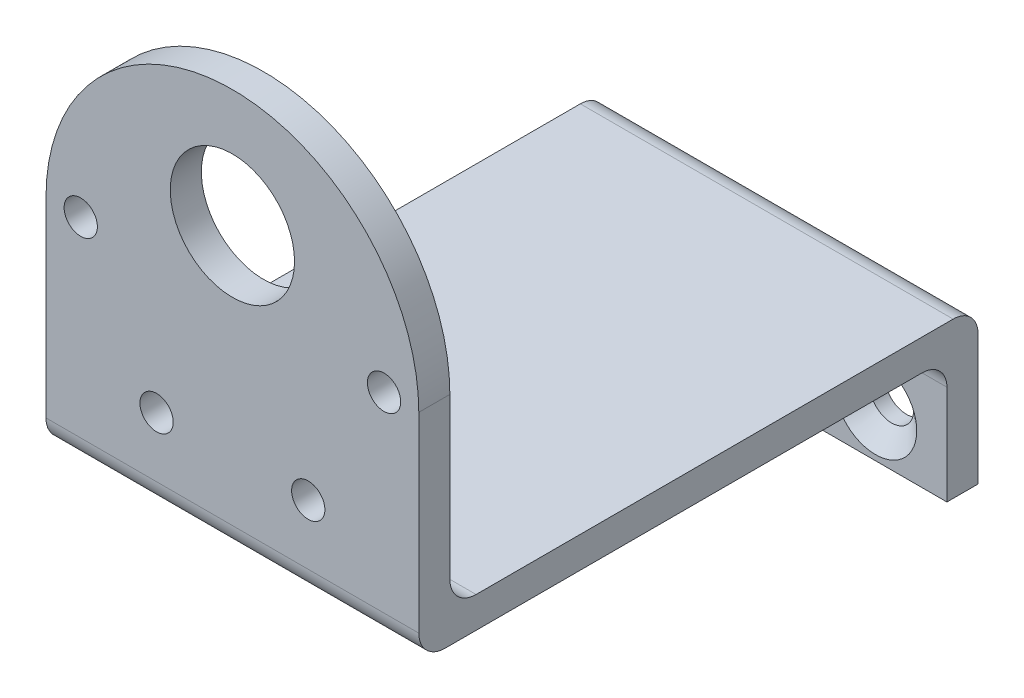
SolidWorks part; units mm, degrees
ref_plane "Front Plane" through (0, 0, 0) normal (0, 0, 1) x (1, 0, 0)
ref_plane "Top Plane" through (0, 0, 0) normal (0, 1, 0) x (1, 0, 0)
ref_plane "Right Plane" through (0, 0, 0) normal (1, 0, 0) x (0, 0, -1)
sketch "Sketch1" plane through (0, 0, 0) normal (1, 0, 0) x (0, 0, -1)
  line L0 (0, 42.0944) -> (0, 6.6753)
  line L1 (2.681, 3.9944) -> (51.435, 3.9944)
  line L3 (0, 42.0944) -> (-3.175, 42.0944)
  line L4 (-3.175, 42.0944) -> (-3.175, 3.5003)
  line L5 (-0.494, 0.8194) -> (48.26, 0.8194)
  line L8 (53.975, 1.4544) -> (53.975, -11.8806)
  line L9 (53.975, -11.8806) -> (50.8, -11.8806)
  line L10 (50.8, -11.8806) -> (50.8, -1.7206)
  arc A2 (-3.175, 3.5003) -> (-0.494, 0.8194) centre (-0.494, 3.5003) ccw
  arc A3 (0, 6.6753) -> (2.681, 3.9944) centre (2.681, 6.6753) ccw
  arc A4 (51.435, 3.9944) -> (53.975, 1.4544) centre (51.435, 1.4544) cw
  arc A5 (48.26, 0.8194) -> (50.8, -1.7206) centre (48.26, -1.7206) cw
  point P14 (52.3875, -11.8806)
  dimension "D2" = 2.54
  dimension "D1" = 3.175
  dimension "D3" = 3.175
  dimension "D4" = 12.7
  dimension "D6" = 57.15
  dimension "D7" = 3.175
  dimension "D5" = 38.1
extrude "Boss-Extrude1" add sketch "Sketch1" along normal blind 38.1 contours L0 A3 L1 A4 L8 L9 L10 A5 L5 A2 L4 L3
hole_wizard "CSK for #8 Flat Head Machine Screw (100)2" positions "Sketch9" profile "Sketch10" countersink size "#8" standard "ANSI Inch" end condition through all
sketch "Sketch9" plane through (0, 0, -50.8) normal (0, 0, 1) x (1, 0, 0)
  line L0 (38.1, -11.8806) -> (0, -11.8806) construction
  point P0 (7.3025, -7.1181)
  point P2 (30.7975, -7.1181)
  point P7 (19.05, -11.8806)
  dimension "D1" = 23.495
  dimension "D2" = 4.7625
  dimension "D3" = 11.7475
sketch "Sketch10" plane through (7.3025, -7.1181, -50.8) normal (1, 0, 0) x (0, -1, 0)
  line L0 (0, 0) -> (0, 3.175)
  line L1 (0, 3.175) -> (2.2479, 3.175)
  line L2 (2.2479, 3.175) -> (2.2479, 1.6518)
  line L3 (2.2479, 1.6518) -> (4.2164, 0)
  line L5 (4.2164, 0) -> (0, 0)
  line L6 (-2.2479, 1.6518) -> (-4.2164, 0) construction
  line L11 (0, -6.35) -> (0, 107.95) construction
  dimension "Thru Hole Dia." = 4.4958
  dimension "Thru Hole Depth" = 3.175
  dimension "Near C'Sink Dia." = 8.4328
  dimension "Near C'Sink Angle" = 100
sketch "Sketch11" plane through (0, 0, 3.175) normal (0, 0, 1) x (1, 0, 0)
  line L0 (38.1, 42.0944) -> (0, 42.0944) construction
  line L1 (38.1, 42.0944) -> (38.1, 3.5003) construction
  line L4 (0, 23.0444) -> (0, 42.0944)
  line L5 (0, 42.0944) -> (38.1, 42.0944)
  line L6 (38.1, 23.0444) -> (38.1, 42.0944)
  arc A0 (38.1, 23.0444) -> (0, 23.0444) centre (19.05, 23.0444) ccw
  circle A3 centre (19.05, 30.0444) radius 6.35
  point P5 (19.05, 42.0944)
  line M2 (0, 42.0944) -> (0, 3.5003)
  line M4 (38.1, 3.5003) -> (38.1, 42.0944)
  line M5 (38.1, 42.0944) -> (0, 42.0944)
  dimension "D2" = 7
  dimension "D1" = 12.7
extrude "Cut-Extrude1" cut sketch "Sketch11" against normal through all contours A0 M4 M5 | A0 L5 M2 | A3 | A3 region at (33.8448, 37.8392, 3.175) region at (4.2552, 37.8392, 3.175) region at (19.05, 30.0444, 3.175)
sketch "Sketch12" plane through (0, 0, 3.175) normal (0, 0, 1) x (1, 0, 0)
  circle A0 centre (19.05, 23.0444) radius 15.5 construction
  point P3 (3.55, 23.0444)
  point P6 (11.3, 9.621)
  point P7 (26.8, 9.621)
  point P8 (34.55, 23.0444)
  point P9 (26.8, 36.4678)
  point P10 (11.3, 36.4678)
  point P11 (19.05, 23.0444)
  dimension "D1" = 31
  dimension "D2" = 6
hole_wizard "M3 Clearance Hole1" positions "Sketch13" profile "Sketch14" hole size "M3" standard "ANSI Metric" end condition through all
sketch "Sketch13" plane through (0, 0, 3.175) normal (0, 0, 1) x (1, 0, 0)
  point P0 (3.55, 23.0444)
  point P9 (34.55, 23.0444)
  point P12 (26.8, 9.621)
  point P15 (11.3, 9.621)
  point P20 (0, 0)
  point P21 (0, 0)
sketch "Sketch14" plane through (3.55, 23.0444, 3.175) normal (1, 0, 0) x (0, -1, 0)
  line L0 (0, 0) -> (0, 57.15)
  line L1 (0, 57.15) -> (1.7, 57.15)
  line L2 (1.7, 57.15) -> (1.7, 0)
  line L5 (1.7, 0) -> (0, 0)
  line L11 (0, -6.35) -> (0, 107.95) construction
  dimension "Thru Hole Dia." = 3.4
  dimension "Thru Hole Depth" = 57.15
equation "\"D3@Sketch1\"=\"D1@Sketch1\""
equation "\"D7@Sketch1\"=\"D1@Sketch1\""
equation "\"D3@Sketch9\"=\"D1@Sketch9\"/2"
